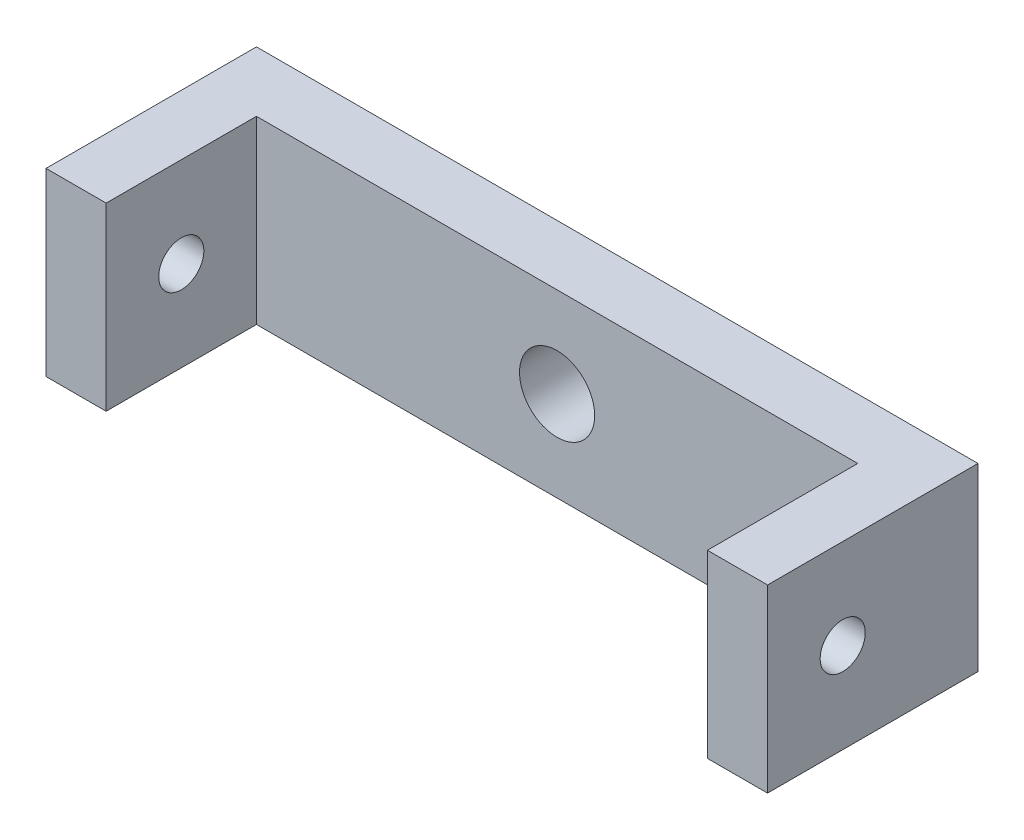
SolidWorks part; units mm, degrees
ref_plane "Front Plane" through (0, 0, 0) normal (0, 0, 1) x (1, 0, 0)
ref_plane "Top Plane" through (0, 0, 0) normal (0, 1, 0) x (1, 0, 0)
ref_plane "Right Plane" through (0, 0, 0) normal (1, 0, 0) x (0, 0, -1)
ref_plane "Plane1" through (0, 0, -19) normal (0, 0, 1) x (1, 0, 0)
sketch "Sketch2" plane through (0, 0, -19) normal (0, 0, 1) x (1, 0, 0)
  line L0 (4.7285, -25.8412) -> (4.7285, -37.8352) construction
  line L1 (28.7285, -25.8412) -> (-19.2715, -25.8412) construction
  line L2 (28.7285, -37.8352) -> (-19.2715, -37.8352) construction
  line L4 (-19.2715, -25.8412) -> (28.7285, -25.8412)
  line L5 (-19.2715, -25.8412) -> (-19.2715, -37.8352)
  line L6 (-19.2715, -37.8352) -> (28.7285, -37.8352)
  line L7 (28.7285, -25.8412) -> (28.7285, -37.8352)
  circle A0 centre (4.7285, -31.8382) radius 2.5
  arc A2 (7.2284, -37.2893) -> (2.2286, -37.2893) centre (4.7285, -31.8382) ccw construction
  circle A3 centre (4.7285, -31.8382) radius 5.997 construction
  point P6 (4.7285, -25.8412)
  point P18 (4.7285, -37.8352)
  dimension "D1" = 48
extrude "Boss-Extrude1" add sketch "Sketch2" along normal blind 4
sketch "Sketch3" plane through (0, 0, -15) normal (0, 0, 1) x (1, 0, 0)
  line L0 (-19.2715, -37.8352) -> (28.7285, -37.8352) construction
  line L1 (28.7285, -25.8412) -> (24.7285, -25.8412)
  line L2 (28.7285, -25.8412) -> (28.7285, -37.8352)
  line L3 (28.7285, -37.8352) -> (24.7285, -37.8352)
  line L4 (24.7285, -25.8412) -> (24.7285, -37.8352)
  line L5 (4.7285, -25.8412) -> (4.7285, -37.8352) construction
  line L6 (28.7285, -25.8412) -> (-19.2715, -25.8412) construction
  line L7 (-19.2715, -37.8352) -> (-15.2715, -37.8352)
  line L8 (-15.2715, -25.8412) -> (-15.2715, -37.8352)
  line L9 (-19.2715, -25.8412) -> (-15.2715, -25.8412)
  line L10 (-19.2715, -25.8412) -> (-19.2715, -37.8352)
extrude "Boss-Extrude2" add sketch "Sketch3" along normal blind 10
sketch "Sketch4" plane through (24.7285, 0, 0) normal (-1, 0, 0) x (0, 0, 1)
  line L0 (-15, -25.8412) -> (-5, -37.8352) construction
  line L1 (-5, -37.8352) -> (-5, -25.8412) construction
  line L2 (-5, -25.8412) -> (-15, -37.8352) construction
  circle A0 centre (-10, -31.8382) radius 1.5
  dimension "D1" = 3
extrude "Cut-Extrude1" cut sketch "Sketch4" against normal through all both and the other way through all
